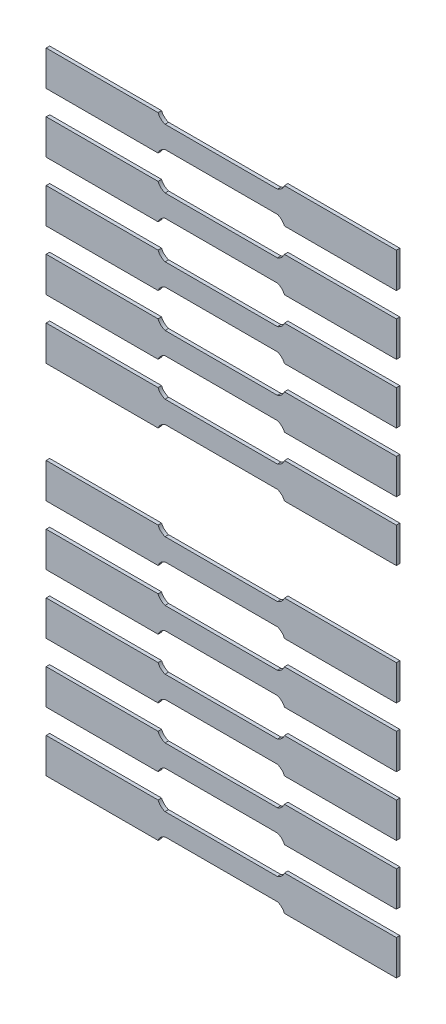
SolidWorks part; units mm, degrees
ref_plane "Ground Plane" through (0, 0, 0) normal (0, 0, 1) x (1, 0, 0)
ref_plane "Center Plane" through (0, 0, 0) normal (0, 1, 0) x (1, 0, 0)
ref_plane "Left Plane" through (0, 0, 0) normal (1, 0, 0) x (0, 0, -1)
ref_axis "FRONT (X)" through (88.99, 0, 0) along (-1, 0, 0)
ref_axis "LEFT (Y)" through (0, 55, 0) along (0, -1, 0)
ref_axis "UP (Z)" through (0, 0, 55) along (0, 0, -1)
sketch "Sketch1" plane through (0, 0, 0) normal (0, 0, 1) x (1, 0, 0)
  line L0 (0, 10) -> (0, 0)
  line L1 (66, 1.875) -> (66.044, 1.875)
  line L2 (66, 8.125) -> (66.044, 8.125)
  line L3 (34, 1.875) -> (33.956, 1.875)
  line L4 (0, 27) -> (0, 17)
  line L5 (66, 18.875) -> (66.044, 18.875)
  line L6 (66, 25.125) -> (66.044, 25.125)
  line L7 (34, 18.875) -> (33.956, 18.875)
  line L8 (0, 17) -> (31.956, 17)
  line L9 (0, 27) -> (31.956, 27)
  line L10 (100, 17) -> (100, 27)
  line L11 (49.956, 25.125) -> (66, 25.125)
  line L12 (66, 18.875) -> (50, 18.875)
  line L13 (50, 18.875) -> (34, 18.875)
  line L14 (33.956, 25.125) -> (49.956, 25.125)
  line L15 (68.044, 27) -> (100, 27)
  line L16 (68.044, 17) -> (100, 17)
  line L17 (0, 0) -> (31.956, 0)
  line L18 (0, 10) -> (31.956, 10)
  line L19 (100, 0) -> (100, 10)
  line L20 (49.956, 8.125) -> (66, 8.125)
  line L21 (66, 1.875) -> (50, 1.875)
  line L22 (50, 1.875) -> (34, 1.875)
  line L23 (33.956, 8.125) -> (49.956, 8.125)
  line L24 (68.044, 10) -> (100, 10)
  line L25 (68.044, 0) -> (100, 0)
  line L26 (33.956, 1.875) -> (31.956, 1.875) construction
  line L27 (31.956, 1.875) -> (31.956, 0) construction
  line L28 (33.956, 8.125) -> (31.956, 8.125) construction
  line L29 (31.956, 8.125) -> (31.956, 10) construction
  line L30 (68.044, 0) -> (68.044, 1.875) construction
  line L31 (68.044, 1.875) -> (66.044, 1.875) construction
  line L32 (66.044, 8.125) -> (68.044, 8.125) construction
  line L33 (68.044, 8.125) -> (68.044, 10) construction
  line L34 (33.956, 18.875) -> (31.956, 18.875) construction
  line L35 (31.956, 18.875) -> (31.956, 17) construction
  line L36 (33.956, 25.125) -> (31.956, 25.125) construction
  line L37 (31.956, 25.125) -> (31.956, 27) construction
  line L38 (68.044, 17) -> (68.044, 18.875) construction
  line L39 (68.044, 18.875) -> (66.044, 18.875) construction
  line L40 (66.044, 25.125) -> (68.044, 25.125) construction
  line L41 (68.044, 25.125) -> (68.044, 27) construction
  line L42 (0, 44) -> (0, 34)
  line L43 (66, 35.875) -> (66.044, 35.875)
  line L44 (66, 42.125) -> (66.044, 42.125)
  line L45 (34, 35.875) -> (33.956, 35.875)
  line L46 (0, 34) -> (31.956, 34)
  line L47 (0, 44) -> (31.956, 44)
  line L48 (100, 34) -> (100, 44)
  line L49 (49.956, 42.125) -> (66, 42.125)
  line L50 (66, 35.875) -> (50, 35.875)
  line L51 (50, 35.875) -> (34, 35.875)
  line L52 (33.956, 42.125) -> (49.956, 42.125)
  line L53 (68.044, 44) -> (100, 44)
  line L54 (68.044, 34) -> (100, 34)
  line L55 (33.956, 35.875) -> (31.956, 35.875) construction
  line L56 (31.956, 35.875) -> (31.956, 34) construction
  line L57 (33.956, 42.125) -> (31.956, 42.125) construction
  line L58 (31.956, 42.125) -> (31.956, 44) construction
  line L59 (68.044, 34) -> (68.044, 35.875) construction
  line L60 (68.044, 35.875) -> (66.044, 35.875) construction
  line L61 (66.044, 42.125) -> (68.044, 42.125) construction
  line L62 (68.044, 42.125) -> (68.044, 44) construction
  line L63 (0, 61) -> (0, 51)
  line L64 (66, 52.875) -> (66.044, 52.875)
  line L65 (66, 59.125) -> (66.044, 59.125)
  line L66 (34, 52.875) -> (33.956, 52.875)
  line L67 (0, 51) -> (31.956, 51)
  line L68 (0, 61) -> (31.956, 61)
  line L69 (100, 51) -> (100, 61)
  line L70 (49.956, 59.125) -> (66, 59.125)
  line L71 (66, 52.875) -> (50, 52.875)
  line L72 (50, 52.875) -> (34, 52.875)
  line L73 (33.956, 59.125) -> (49.956, 59.125)
  line L74 (68.044, 61) -> (100, 61)
  line L75 (68.044, 51) -> (100, 51)
  line L76 (33.956, 52.875) -> (31.956, 52.875) construction
  line L77 (31.956, 52.875) -> (31.956, 51) construction
  line L78 (33.956, 59.125) -> (31.956, 59.125) construction
  line L79 (31.956, 59.125) -> (31.956, 61) construction
  line L80 (68.044, 51) -> (68.044, 52.875) construction
  line L81 (68.044, 52.875) -> (66.044, 52.875) construction
  line L82 (66.044, 59.125) -> (68.044, 59.125) construction
  line L83 (68.044, 59.125) -> (68.044, 61) construction
  line L84 (0, 78) -> (0, 68)
  line L85 (66, 69.875) -> (66.044, 69.875)
  line L86 (66, 76.125) -> (66.044, 76.125)
  line L87 (34, 69.875) -> (33.956, 69.875)
  line L88 (0, 68) -> (31.956, 68)
  line L89 (0, 78) -> (31.956, 78)
  line L90 (100, 68) -> (100, 78)
  line L91 (49.956, 76.125) -> (66, 76.125)
  line L92 (66, 69.875) -> (50, 69.875)
  line L93 (50, 69.875) -> (34, 69.875)
  line L94 (33.956, 76.125) -> (49.956, 76.125)
  line L95 (68.044, 78) -> (100, 78)
  line L96 (68.044, 68) -> (100, 68)
  line L97 (33.956, 69.875) -> (31.956, 69.875) construction
  line L98 (31.956, 69.875) -> (31.956, 68) construction
  line L99 (33.956, 76.125) -> (31.956, 76.125) construction
  line L100 (31.956, 76.125) -> (31.956, 78) construction
  line L101 (68.044, 68) -> (68.044, 69.875) construction
  line L102 (68.044, 69.875) -> (66.044, 69.875) construction
  line L103 (66.044, 76.125) -> (68.044, 76.125) construction
  line L104 (68.044, 76.125) -> (68.044, 78) construction
  line L126 (0, 112) -> (0, 102)
  line L127 (66, 103.875) -> (66.044, 103.875)
  line L128 (66, 110.125) -> (66.044, 110.125)
  line L129 (34, 103.875) -> (33.956, 103.875)
  line L130 (0, 102) -> (31.956, 102)
  line L131 (0, 112) -> (31.956, 112)
  line L132 (100, 102) -> (100, 112)
  line L133 (49.956, 110.125) -> (66, 110.125)
  line L134 (66, 103.875) -> (50, 103.875)
  line L135 (50, 103.875) -> (34, 103.875)
  line L136 (33.956, 110.125) -> (49.956, 110.125)
  line L137 (68.044, 112) -> (100, 112)
  line L138 (68.044, 102) -> (100, 102)
  line L139 (33.956, 103.875) -> (31.956, 103.875) construction
  line L140 (31.956, 103.875) -> (31.956, 102) construction
  line L141 (33.956, 110.125) -> (31.956, 110.125) construction
  line L142 (31.956, 110.125) -> (31.956, 112) construction
  line L143 (68.044, 102) -> (68.044, 103.875) construction
  line L144 (68.044, 103.875) -> (66.044, 103.875) construction
  line L145 (66.044, 110.125) -> (68.044, 110.125) construction
  line L146 (68.044, 110.125) -> (68.044, 112) construction
  line L147 (0, 129) -> (0, 119)
  line L148 (66, 120.875) -> (66.044, 120.875)
  line L149 (66, 127.125) -> (66.044, 127.125)
  line L150 (34, 120.875) -> (33.956, 120.875)
  line L151 (0, 119) -> (31.956, 119)
  line L152 (0, 129) -> (31.956, 129)
  line L153 (100, 119) -> (100, 129)
  line L154 (49.956, 127.125) -> (66, 127.125)
  line L155 (66, 120.875) -> (50, 120.875)
  line L156 (50, 120.875) -> (34, 120.875)
  line L157 (33.956, 127.125) -> (49.956, 127.125)
  line L158 (68.044, 129) -> (100, 129)
  line L159 (68.044, 119) -> (100, 119)
  line L160 (33.956, 120.875) -> (31.956, 120.875) construction
  line L161 (31.956, 120.875) -> (31.956, 119) construction
  line L162 (33.956, 127.125) -> (31.956, 127.125) construction
  line L163 (31.956, 127.125) -> (31.956, 129) construction
  line L164 (68.044, 119) -> (68.044, 120.875) construction
  line L165 (68.044, 120.875) -> (66.044, 120.875) construction
  line L166 (66.044, 127.125) -> (68.044, 127.125) construction
  line L167 (68.044, 127.125) -> (68.044, 129) construction
  line L168 (0, 146) -> (0, 136)
  line L169 (66, 137.875) -> (66.044, 137.875)
  line L170 (66, 144.125) -> (66.044, 144.125)
  line L171 (34, 137.875) -> (33.956, 137.875)
  line L172 (0, 136) -> (31.956, 136)
  line L173 (0, 146) -> (31.956, 146)
  line L174 (100, 136) -> (100, 146)
  line L175 (49.956, 144.125) -> (66, 144.125)
  line L176 (66, 137.875) -> (50, 137.875)
  line L177 (50, 137.875) -> (34, 137.875)
  line L178 (33.956, 144.125) -> (49.956, 144.125)
  line L179 (68.044, 146) -> (100, 146)
  line L180 (68.044, 136) -> (100, 136)
  line L181 (33.956, 137.875) -> (31.956, 137.875) construction
  line L182 (31.956, 137.875) -> (31.956, 136) construction
  line L183 (33.956, 144.125) -> (31.956, 144.125) construction
  line L184 (31.956, 144.125) -> (31.956, 146) construction
  line L185 (68.044, 136) -> (68.044, 137.875) construction
  line L186 (68.044, 137.875) -> (66.044, 137.875) construction
  line L187 (66.044, 144.125) -> (68.044, 144.125) construction
  line L188 (68.044, 144.125) -> (68.044, 146) construction
  line L189 (0, 163) -> (0, 153)
  line L190 (66, 154.875) -> (66.044, 154.875)
  line L191 (66, 161.125) -> (66.044, 161.125)
  line L192 (34, 154.875) -> (33.956, 154.875)
  line L193 (0, 153) -> (31.956, 153)
  line L194 (0, 163) -> (31.956, 163)
  line L195 (100, 153) -> (100, 163)
  line L196 (49.956, 161.125) -> (66, 161.125)
  line L197 (66, 154.875) -> (50, 154.875)
  line L198 (50, 154.875) -> (34, 154.875)
  line L199 (33.956, 161.125) -> (49.956, 161.125)
  line L200 (68.044, 163) -> (100, 163)
  line L201 (68.044, 153) -> (100, 153)
  line L202 (33.956, 154.875) -> (31.956, 154.875) construction
  line L203 (31.956, 154.875) -> (31.956, 153) construction
  line L204 (33.956, 161.125) -> (31.956, 161.125) construction
  line L205 (31.956, 161.125) -> (31.956, 163) construction
  line L206 (68.044, 153) -> (68.044, 154.875) construction
  line L207 (68.044, 154.875) -> (66.044, 154.875) construction
  line L208 (66.044, 161.125) -> (68.044, 161.125) construction
  line L209 (68.044, 161.125) -> (68.044, 163) construction
  line L210 (0, 180) -> (0, 170)
  line L211 (66, 171.875) -> (66.044, 171.875)
  line L212 (66, 178.125) -> (66.044, 178.125)
  line L213 (34, 171.875) -> (33.956, 171.875)
  line L214 (0, 170) -> (31.956, 170)
  line L215 (0, 180) -> (31.956, 180)
  line L216 (100, 170) -> (100, 180)
  line L217 (49.956, 178.125) -> (66, 178.125)
  line L218 (66, 171.875) -> (50, 171.875)
  line L219 (50, 171.875) -> (34, 171.875)
  line L220 (33.956, 178.125) -> (49.956, 178.125)
  line L221 (68.044, 180) -> (100, 180)
  line L222 (68.044, 170) -> (100, 170)
  line L223 (33.956, 171.875) -> (31.956, 171.875) construction
  line L224 (31.956, 171.875) -> (31.956, 170) construction
  line L225 (33.956, 178.125) -> (31.956, 178.125) construction
  line L226 (31.956, 178.125) -> (31.956, 180) construction
  line L227 (68.044, 170) -> (68.044, 171.875) construction
  line L228 (68.044, 171.875) -> (66.044, 171.875) construction
  line L229 (66.044, 178.125) -> (68.044, 178.125) construction
  line L230 (68.044, 178.125) -> (68.044, 180) construction
  line L231 (0, 95) -> (0, 85) [skipped]
  line L232 (66, 86.875) -> (66.044, 86.875) [skipped]
  line L233 (66, 93.125) -> (66.044, 93.125) [skipped]
  line L234 (34, 86.875) -> (33.956, 86.875) [skipped]
  line L235 (0, 85) -> (31.956, 85) [skipped]
  line L236 (0, 95) -> (31.956, 95) [skipped]
  line L237 (100, 85) -> (100, 95) [skipped]
  line L238 (49.956, 93.125) -> (66, 93.125) [skipped]
  line L239 (66, 86.875) -> (50, 86.875) [skipped]
  line L240 (50, 86.875) -> (34, 86.875) [skipped]
  line L241 (33.956, 93.125) -> (49.956, 93.125) [skipped]
  line L242 (68.044, 95) -> (100, 95) [skipped]
  line L243 (68.044, 85) -> (100, 85) [skipped]
  line L244 (33.956, 86.875) -> (31.956, 86.875) construction
  line L245 (31.956, 86.875) -> (31.956, 85) construction
  line L246 (33.956, 93.125) -> (31.956, 93.125) construction
  line L247 (31.956, 93.125) -> (31.956, 95) construction
  line L248 (68.044, 85) -> (68.044, 86.875) construction
  line L249 (68.044, 86.875) -> (66.044, 86.875) construction
  line L250 (66.044, 93.125) -> (68.044, 93.125) construction
  line L251 (68.044, 93.125) -> (68.044, 95) construction
  arc A0 (33.956, 25.125) -> (31.956, 27) centre (34.9695, 28.2102) cw
  arc A1 (33.956, 18.875) -> (31.956, 17) centre (34.9695, 15.7898) ccw
  arc A2 (66.044, 18.875) -> (68.044, 17) centre (65.0305, 15.7898) cw
  arc A3 (66.044, 25.125) -> (68.044, 27) centre (65.0305, 28.2102) ccw
  arc A4 (33.956, 8.125) -> (31.956, 10) centre (34.9695, 11.2102) cw
  arc A5 (33.956, 1.875) -> (31.956, 0) centre (34.9695, -1.2102) ccw
  arc A6 (66.044, 1.875) -> (68.044, 0) centre (65.0305, -1.2102) cw
  arc A7 (66.044, 8.125) -> (68.044, 10) centre (65.0305, 11.2102) ccw
  arc A8 (33.956, 42.125) -> (31.956, 44) centre (34.9695, 45.2102) cw
  arc A9 (33.956, 35.875) -> (31.956, 34) centre (34.9695, 32.7898) ccw
  arc A10 (66.044, 35.875) -> (68.044, 34) centre (65.0305, 32.7898) cw
  arc A11 (66.044, 42.125) -> (68.044, 44) centre (65.0305, 45.2102) ccw
  arc A12 (33.956, 59.125) -> (31.956, 61) centre (34.9695, 62.2102) cw
  arc A13 (33.956, 52.875) -> (31.956, 51) centre (34.9695, 49.7898) ccw
  arc A14 (66.044, 52.875) -> (68.044, 51) centre (65.0305, 49.7898) cw
  arc A15 (66.044, 59.125) -> (68.044, 61) centre (65.0305, 62.2102) ccw
  arc A16 (33.956, 76.125) -> (31.956, 78) centre (34.9695, 79.2102) cw
  arc A17 (33.956, 69.875) -> (31.956, 68) centre (34.9695, 66.7898) ccw
  arc A18 (66.044, 69.875) -> (68.044, 68) centre (65.0305, 66.7898) cw
  arc A19 (66.044, 76.125) -> (68.044, 78) centre (65.0305, 79.2102) ccw
  arc A24 (33.956, 110.125) -> (31.956, 112) centre (34.9695, 113.2102) cw
  arc A25 (33.956, 103.875) -> (31.956, 102) centre (34.9695, 100.7898) ccw
  arc A26 (66.044, 103.875) -> (68.044, 102) centre (65.0305, 100.7898) cw
  arc A27 (66.044, 110.125) -> (68.044, 112) centre (65.0305, 113.2102) ccw
  arc A28 (33.956, 127.125) -> (31.956, 129) centre (34.9695, 130.2102) cw
  arc A29 (33.956, 120.875) -> (31.956, 119) centre (34.9695, 117.7898) ccw
  arc A30 (66.044, 120.875) -> (68.044, 119) centre (65.0305, 117.7898) cw
  arc A31 (66.044, 127.125) -> (68.044, 129) centre (65.0305, 130.2102) ccw
  arc A32 (33.956, 144.125) -> (31.956, 146) centre (34.9695, 147.2102) cw
  arc A33 (33.956, 137.875) -> (31.956, 136) centre (34.9695, 134.7898) ccw
  arc A34 (66.044, 137.875) -> (68.044, 136) centre (65.0305, 134.7898) cw
  arc A35 (66.044, 144.125) -> (68.044, 146) centre (65.0305, 147.2102) ccw
  arc A36 (33.956, 161.125) -> (31.956, 163) centre (34.9695, 164.2102) cw
  arc A37 (33.956, 154.875) -> (31.956, 153) centre (34.9695, 151.7898) ccw
  arc A38 (66.044, 154.875) -> (68.044, 153) centre (65.0305, 151.7898) cw
  arc A39 (66.044, 161.125) -> (68.044, 163) centre (65.0305, 164.2102) ccw
  arc A40 (33.956, 178.125) -> (31.956, 180) centre (34.9695, 181.2102) cw
  arc A41 (33.956, 171.875) -> (31.956, 170) centre (34.9695, 168.7898) ccw
  arc A42 (66.044, 171.875) -> (68.044, 170) centre (65.0305, 168.7898) cw
  arc A43 (66.044, 178.125) -> (68.044, 180) centre (65.0305, 181.2102) ccw
  arc A44 (33.956, 93.125) -> (31.956, 95) centre (34.9695, 96.2102) cw [skipped]
  arc A45 (33.956, 86.875) -> (31.956, 85) centre (34.9695, 83.7898) ccw [skipped]
  arc A46 (66.044, 86.875) -> (68.044, 85) centre (65.0305, 83.7898) cw [skipped]
  arc A47 (66.044, 93.125) -> (68.044, 95) centre (65.0305, 96.2102) ccw [skipped]
  point P52 (32.956, 1.875)
  dimension "D1" = 100
  dimension "D2" = 10
  dimension "D3" = 11
extrude "Boss-Extrude1" add sketch "Sketch1" against normal blind 1
